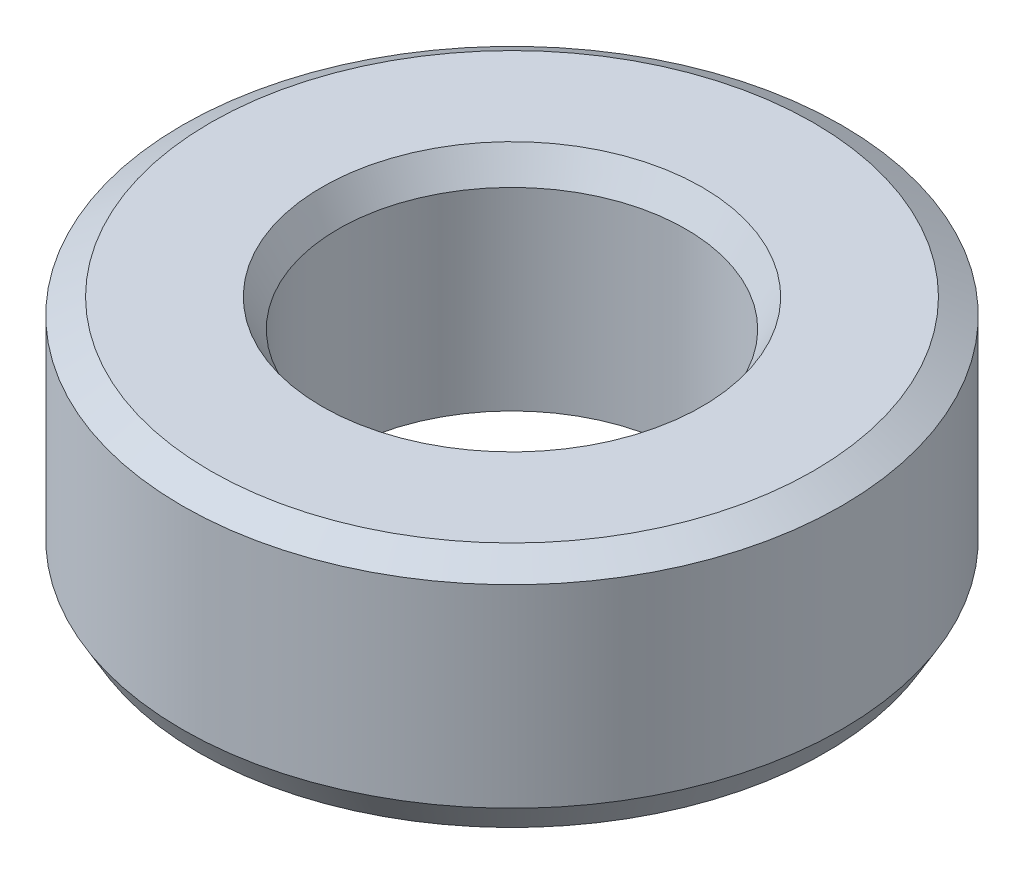
SolidWorks part; units mm, degrees
ref_plane "Front Plane" through (0, 0, 0) normal (0, 0, 1) x (1, 0, 0)
ref_plane "Top Plane" through (0, 0, 0) normal (0, 1, 0) x (1, 0, 0)
ref_plane "Right Plane" through (0, 0, 0) normal (1, 0, 0) x (0, 0, -1)
sketch "Sketch1" plane through (0, 0, 0) normal (0, 1, 0) x (1, 0, 0)
  circle A0 centre (0, 0) radius 47.5
  dimension "SLEEVE_OD" = 95
extrude "Boss-Extrude1" add sketch "Sketch1" along normal blind 34.2864
sketch "Sketch2" plane through (0, 0, 0) normal (0, 1, 0) x (1, 0, 0)
  circle A0 centre (0, 0) radius 25.0352
  dimension "BORE_D" = 50.0704
extrude "Cut-Extrude1" cut sketch "Sketch2" along normal through all
chamfer "Chamfer1" distance 2.3403 angle 60 4 edges at (0, 34.2864, 25.0352) (0, 0, 25.0352) (0, 0, 47.5) (0, 34.2864, 47.5) first distance on face at (0, 34.2864, 25.0352) first distance on face at (0, 0, 25.0352) first distance on face at (0, 34.2864, 47.5)
